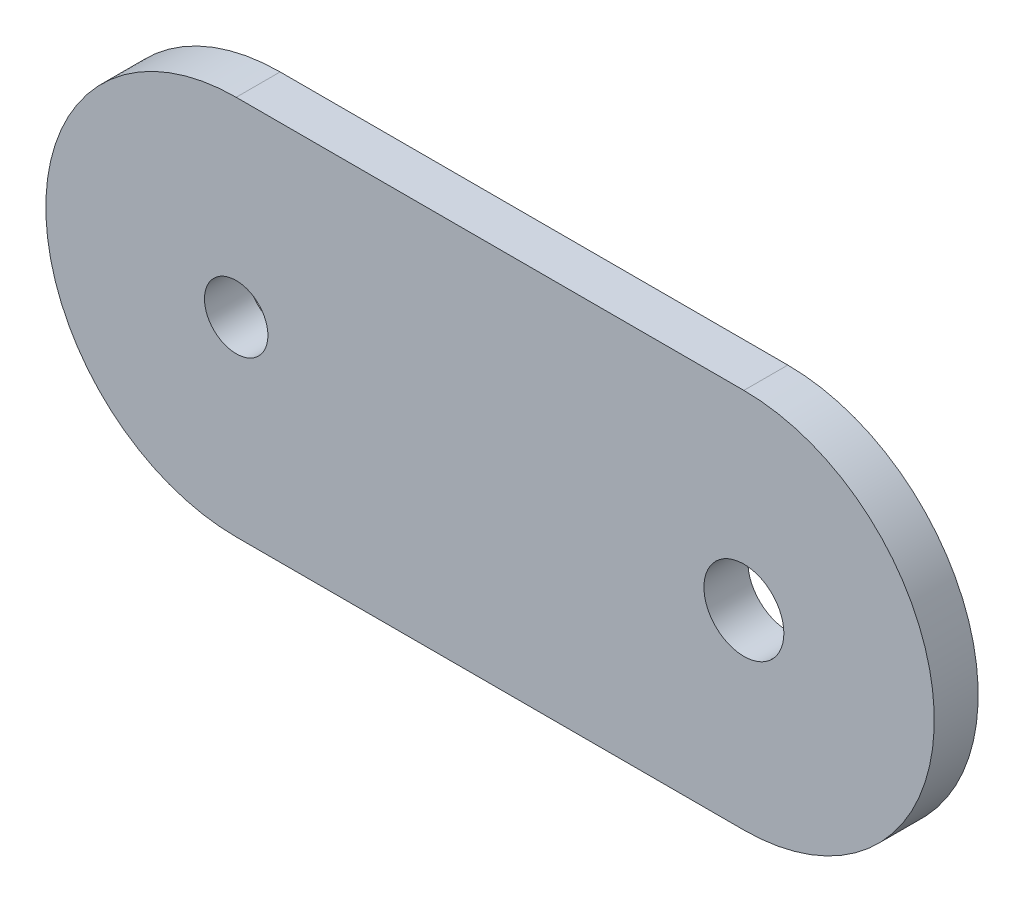
SolidWorks part; units mm, degrees
ref_plane "Front Plane" through (0, 0, 0) normal (0, 0, 1) x (1, 0, 0)
ref_plane "Top Plane" through (0, 0, 0) normal (0, 1, 0) x (1, 0, 0)
ref_plane "Right Plane" through (0, 0, 0) normal (1, 0, 0) x (0, 0, -1)
sketch "Sketch1" plane through (0, 0, 0) normal (0, 0, 1) x (1, 0, 0)
  line L0 (0, 0) -> (50.8, 0) construction
  line L1 (0, 19.05) -> (50.8, 19.05)
  line L2 (0, -19.05) -> (50.8, -19.05)
  arc A0 (0, 19.05) -> (0, -19.05) centre (0, 0) ccw
  arc A1 (50.8, -19.05) -> (50.8, 19.05) centre (50.8, 0) ccw
  circle A2 centre (0, 0) radius 3.175
  circle A3 centre (50.8, 0) radius 4
  point P3 (25.4, 0)
  dimension "D3" = 6.35
  dimension "D4" = 8
  dimension "D1" = 50.8
  dimension "D2" = 38.1
extrude "Boss-Extrude1" add sketch "Sketch1" along normal blind 4.3942
